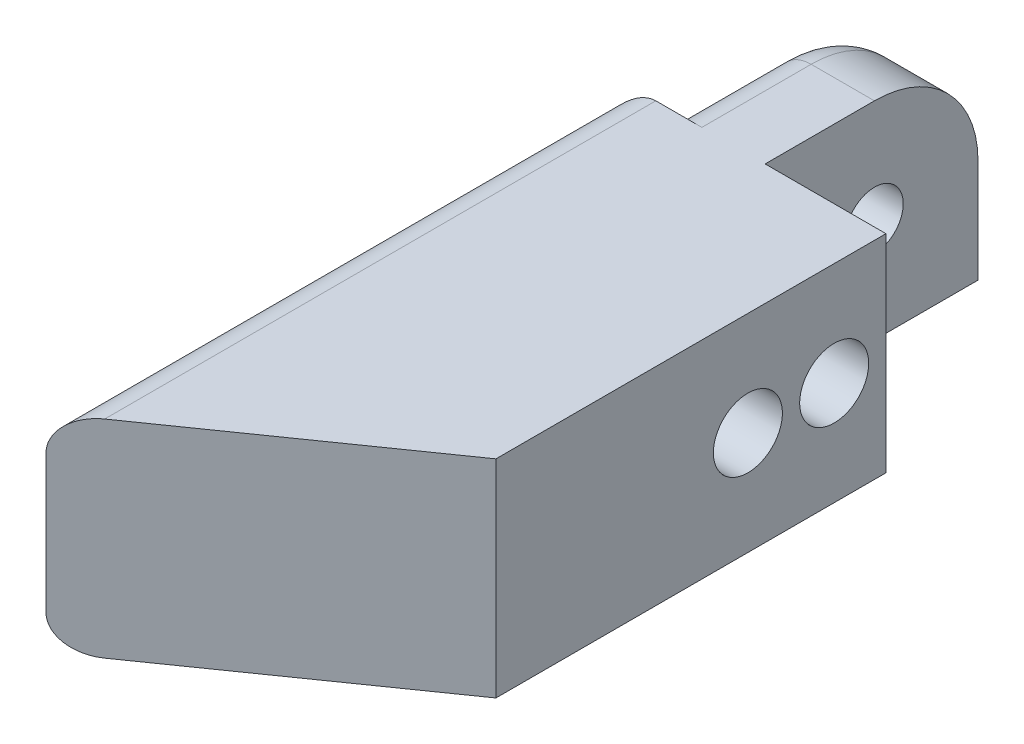
SolidWorks part; units mm, degrees
ref_plane "Front Plane" through (0, 0, 0) normal (0, 0, 1) x (1, 0, 0)
ref_plane "Top Plane" through (0, 0, 0) normal (0, 1, 0) x (1, 0, 0)
ref_plane "Right Plane" through (0, 0, 0) normal (1, 0, 0) x (0, 0, -1)
sketch "Sketch1" plane through (0, 0, 0) normal (0, 1, 0) x (1, 0, 0)
  line L0 (-8.25, 16.9476) -> (-8.25, -33.0524)
  line L1 (-8.25, -33.0524) -> (14.75, -16.9476)
  line L2 (14.75, -16.9476) -> (14.75, 16.9476)
  line L3 (14.75, 16.9476) -> (4.25, 16.9476)
  line L4 (4.25, 16.9476) -> (4.25, 35.4476)
  line L5 (4.25, 35.4476) -> (-4.25, 35.4476)
  line L6 (-4.25, 35.4476) -> (-4.25, 16.9476)
  line L7 (-4.25, 16.9476) -> (-8.25, 16.9476)
  line L8 (-8.25, 0) -> (14.75, 0) construction
  line L9 (0, 35.4476) -> (0, -27.2757) construction
  dimension "D1" = 10.5
  dimension "D2" = 4
  dimension "D3" = 8.5
  dimension "D4" = 18.5
  dimension "D5" = 50
  dimension "D6" = 55
extrude "Boss-Extrude1" add sketch "Sketch1" along normal blind 18
sketch "Sketch3" plane through (-8.25, 0, 0) normal (-1, 0, 0) x (0, 0, 1)
  line L0 (-26.4476, 18) -> (-26.4476, 0) construction
  line L1 (-35.4476, 9) -> (-35.4476, 18)
  line L2 (-35.4476, 18) -> (-26.4476, 18)
  line L3 (-35.4476, 18) -> (-16.9476, 18) construction
  line L5 (-35.4476, 18) -> (-35.4476, 0) construction
  line L6 (-35.4476, 9) -> (33.0524, 9) construction
  line L7 (33.0524, 18) -> (33.0524, 0) construction
  line L8 (-16.9476, 18) -> (-16.9476, 0) construction
  arc A0 (-26.4476, 18) -> (-35.4476, 9) centre (-26.4476, 9) ccw
  circle A1 centre (-26.4476, 9) radius 2.5
  circle A2 centre (-12.4476, 9) radius 3
  circle A3 centre (-4.9476, 9) radius 3
  point P2 (-26.4476, 9)
  point P13 (-12.4476, 9)
  point P14 (-4.9476, 9)
  dimension "D4" = 6
  dimension "D5" = 5
  dimension "D1" = 9
  dimension "D2" = 4.5
  dimension "D3" = 7.5
extrude "Cut-Extrude1" cut sketch "Sketch3" against normal through all
fillet "Fillet1" radius 3 3 edges at (-4.25, 18, -21.6976) (-4.25, 15.364, -32.8116) (-4.25, 4.5, -35.4476)
fillet "Fillet2" radius 3 3 edges at (-8.25, 9, -16.9476) (-8.25, 0, 8.0524) (-8.25, 18, 8.0524)
